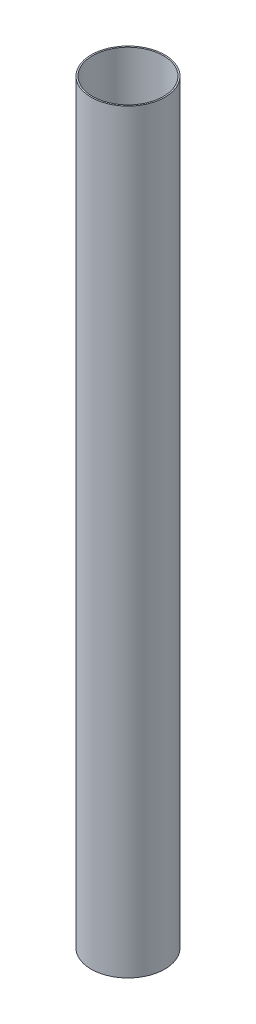
SolidWorks part; units mm, degrees
material "S-Glass Fiber"
ref_plane "Front Plane" through (0, 0, 0) normal (0, 0, 1) x (1, 0, 0)
ref_plane "Top Plane" through (0, 0, 0) normal (0, 1, 0) x (1, 0, 0)
ref_plane "Right Plane" through (0, 0, 0) normal (1, 0, 0) x (0, 0, -1)
sketch "Sketch2" plane through (0, 0, 0) normal (0, 1, 0) x (1, 0, 0)
  circle A0 centre (0, 0) radius 39.624
  circle A1 centre (0, 0) radius 38.1
  dimension "D1" = 79.248
  dimension "D2" = 76.2
extrude "Boss-Extrude1" add sketch "Sketch2" along normal blind 812.8 contours A1 | A0
